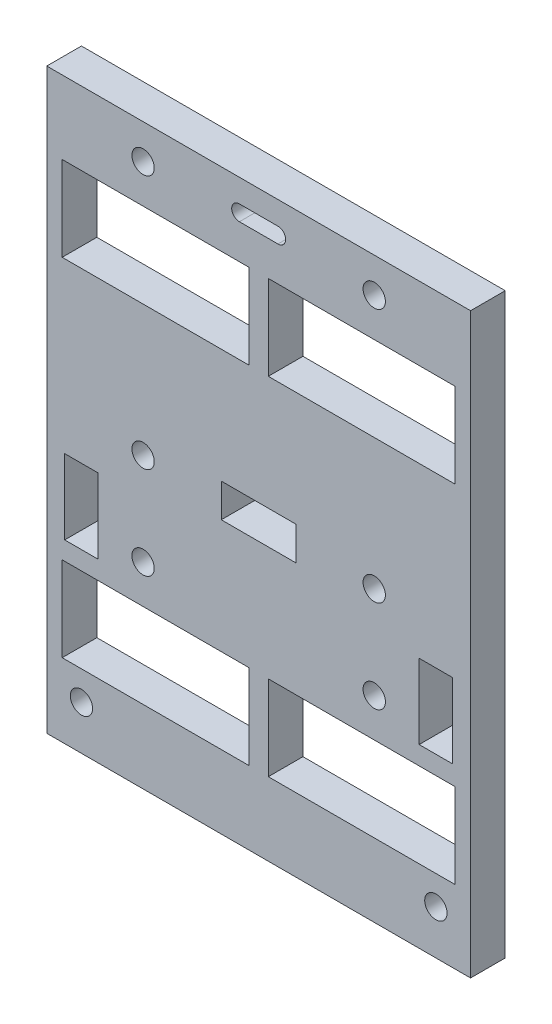
SolidWorks part; units mm, degrees
ref_plane "Front Plane" through (0, 0, 0) normal (0, 0, 1) x (1, 0, 0)
ref_plane "Top Plane" through (0, 0, 0) normal (0, 1, 0) x (1, 0, 0)
ref_plane "Right Plane" through (0, 0, 0) normal (1, 0, 0) x (0, 0, -1)
sketch "Sketch1" plane through (0, 0, 0) normal (0, 0, 1) x (1, 0, 0)
  line L0 (0, -37.5) -> (0, 37.5) construction
  line L1 (-27.5, -37.5) -> (27.5, -37.5)
  line L2 (-27.5, -37.5) -> (-27.5, 37.5)
  line L3 (-27.5, 37.5) -> (27.5, 37.5)
  line L4 (27.5, -37.5) -> (27.5, 37.5)
  line L5 (-27.5, -37.5) -> (27.5, 37.5) construction
  line L6 (-27.5, 37.5) -> (27.5, -37.5) construction
  line L7 (-27.5, 0) -> (27.5, 0) construction
  line L8 (-27.5, 22.5) -> (27.5, 22.5) construction
  line L9 (25.5, 17) -> (1.25, 28) construction
  line L10 (-25.5, 28) -> (-1.25, 28)
  line L11 (-25.5, 28) -> (-25.5, 17)
  line L12 (-25.5, 17) -> (-1.25, 17)
  line L13 (-1.25, 28) -> (-1.25, 17)
  line L14 (-25.5, 28) -> (-1.25, 17) construction
  line L15 (-25.5, 17) -> (-1.25, 28) construction
  line L16 (25.5, 28) -> (1.25, 17) construction
  line L17 (1.25, 28) -> (1.25, 17)
  line L18 (25.5, 17) -> (1.25, 17)
  line L19 (25.5, 28) -> (25.5, 17)
  line L20 (25.5, 28) -> (1.25, 28)
  line L21 (25.5, -28) -> (1.25, -17) construction
  line L22 (-25.5, -17) -> (-1.25, -28) construction
  line L23 (-25.5, -28) -> (-1.25, -17) construction
  line L24 (25.5, -17) -> (1.25, -28) construction
  line L25 (25.5, -28) -> (1.25, -28)
  line L26 (25.5, -28) -> (25.5, -17)
  line L27 (25.5, -17) -> (1.25, -17)
  line L28 (1.25, -28) -> (1.25, -17)
  line L29 (-1.25, -28) -> (-1.25, -17)
  line L30 (-25.5, -17) -> (-1.25, -17)
  line L31 (-25.5, -28) -> (-25.5, -17)
  line L32 (-25.5, -28) -> (-1.25, -28)
  point P0 (0, 0)
  point P12 (-13.375, 22.5)
  point P21 (13.375, 22.5)
  point P30 (13.375, -22.5)
  point P31 (-13.375, -22.5)
  dimension "D1" = 55
  dimension "D2" = 75
  dimension "D3" = 22.5
  dimension "D4" = 24.25
  dimension "D5" = 11
  dimension "D6" = 1.25
extrude "Boss-Extrude1" add sketch "Sketch1" along normal blind 4.5
sketch "Sketch2" plane through (0, 0, 4.5) normal (0, 0, 1) x (1, 0, 0)
  line L0 (0, -37.5) -> (0, 37.5) construction
  line L1 (-27.5, -37.5) -> (27.5, -37.5) construction
  line L2 (27.5, 37.5) -> (-27.5, 37.5) construction
  line L3 (-27.5, 0) -> (27.5, 0) construction
  line L4 (-27.5, 37.5) -> (-27.5, -37.5) construction
  line L5 (27.5, -37.5) -> (27.5, 37.5) construction
  line L6 (-15, 0) -> (15, 0) construction
  circle A0 centre (-15, 33) radius 1.45
  circle A1 centre (15, 33) radius 1.45
  circle A2 centre (15, 0) radius 1.45
  circle A3 centre (-15, 0) radius 1.45
  dimension "D1" = 2.9
  dimension "D7" = 2.9
  dimension "D8" = 2.9
  dimension "D2" = 15
  dimension "D3" = 33
  dimension "D4" = 30
  dimension "D5" = 15
  dimension "D6" = 0
extrude "screwHoles" cut sketch "Sketch2" against normal through all
sketch "Sketch3" plane through (0, 0, 4.5) normal (0, 0, 1) x (1, 0, 0)
  line L0 (-27.5, 9) -> (26.0486, 9) construction
  line L1 (-27.5, 37.5) -> (-27.5, -37.5) construction
  line L3 (0, 37.5) -> (0, -37.5) construction
  line L4 (27.5, 37.5) -> (-27.5, 37.5) construction
  line L5 (-27.5, -37.5) -> (27.5, -37.5) construction
  line L6 (18.95, 6.8) -> (9.05, 11.2) construction
  line L7 (-18.95, 11.2) -> (-9.05, 11.2)
  line L8 (-18.95, 11.2) -> (-18.95, 6.8)
  line L9 (-18.95, 6.8) -> (-9.05, 6.8)
  line L10 (-9.05, 11.2) -> (-9.05, 6.8)
  line L11 (-18.95, 11.2) -> (-9.05, 6.8) construction
  line L12 (-18.95, 6.8) -> (-9.05, 11.2) construction
  line L13 (18.95, 11.2) -> (9.05, 6.8) construction
  line L14 (9.05, 11.2) -> (9.05, 6.8)
  line L15 (18.95, 6.8) -> (9.05, 6.8)
  line L16 (18.95, 11.2) -> (18.95, 6.8)
  line L17 (18.95, 11.2) -> (9.05, 11.2)
  line L18 (-27.5, 37.5) -> (-27.5, -37.5) construction
  point P2 (-27.5, 0)
  point P12 (-14, 9)
  point P21 (14, 9)
  dimension "D1" = 9.9
  dimension "D3" = 14
  dimension "D4" = 9
extrude "BeltClamp" [suppressed] cut sketch "Sketch3" against normal through all
sketch "Sketch4" plane through (0, 0, 4.5) normal (0, 0, 1) x (1, 0, 0)
  line L0 (-27.5, 0) -> (27.5, 0) construction
  line L1 (-27.5, 37.5) -> (-27.5, -37.5) construction
  line L2 (27.5, -37.5) -> (27.5, 37.5) construction
  line L4 (-4.85, 2.175) -> (4.85, 2.175)
  line L5 (-4.85, 2.175) -> (-4.85, -2.175)
  line L6 (-4.85, -2.175) -> (4.85, -2.175)
  line L7 (4.85, 2.175) -> (4.85, -2.175)
  line L8 (-4.85, 2.175) -> (4.85, -2.175) construction
  line L9 (-4.85, -2.175) -> (4.85, 2.175) construction
  circle A0 centre (-15, 0) radius 1.45 construction
  point P6 (0, 0)
  dimension "D2" = 4.35
  dimension "D3" = 0
extrude "mountingPlateTab" cut sketch "Sketch4" against normal through all
sketch "Sketch5" plane through (0, 0, 4.5) normal (0, 0, 1) x (1, 0, 0)
  line L0 (-27.5, -9.75) -> (27.5, -9.75) construction
  line L1 (-27.5, 37.5) -> (-27.5, -37.5) construction
  line L2 (27.5, -37.5) -> (27.5, 37.5) construction
  line L4 (0, -37.5) -> (0, 37.5) construction
  line L5 (-27.5, -37.5) -> (27.5, -37.5) construction
  line L6 (27.5, 37.5) -> (-27.5, 37.5) construction
  line L7 (-20.825, -14.6) -> (-25.175, -4.9) construction
  line L8 (20.825, -4.9) -> (25.175, -4.9)
  line L9 (20.825, -4.9) -> (20.825, -14.6)
  line L10 (20.825, -14.6) -> (25.175, -14.6)
  line L11 (25.175, -4.9) -> (25.175, -14.6)
  line L12 (20.825, -4.9) -> (25.175, -14.6) construction
  line L13 (20.825, -14.6) -> (25.175, -4.9) construction
  line L14 (-20.825, -4.9) -> (-25.175, -14.6) construction
  line L15 (-25.175, -4.9) -> (-25.175, -14.6)
  line L16 (-20.825, -14.6) -> (-25.175, -14.6)
  line L17 (-20.825, -4.9) -> (-20.825, -14.6)
  line L18 (-20.825, -4.9) -> (-25.175, -4.9)
  line L19 (23, -9.75) -> (23, -37.5) construction
  line L20 (-23, -9.75) -> (-23, -37.5) construction
  circle A0 centre (23, -31.75) radius 1.45
  circle A1 centre (-23, -31.75) radius 1.45
  point P15 (23, -9.75)
  point P24 (-23, -9.75)
  dimension "D5" = 2.9
  dimension "D2" = 9.7
  dimension "D3" = 4.35
  dimension "D4" = 23
  dimension "D6" = 22
  dimension "D1" = 9.75
extrude "BraceTabs" cut sketch "Sketch5" against normal through all
sketch "Sketch6" plane through (0, 0, 4.5) normal (0, 0, 1) x (1, 0, 0)
  line L0 (-25.175, -9.75) -> (25.175, -9.75) construction
  line L1 (-25.175, -4.9) -> (-25.175, -14.6) construction
  line L2 (25.175, -14.6) -> (25.175, -4.9) construction
  line L3 (0, -2.175) -> (0, -37.5) construction
  line L4 (-4.85, -2.175) -> (4.85, -2.175) construction
  line L5 (-27.5, -37.5) -> (27.5, -37.5) construction
  line L6 (23, -14.6) -> (23, -4.9) construction
  line L7 (20.825, -14.6) -> (25.175, -14.6) construction
  line L8 (25.175, -4.9) -> (20.825, -4.9) construction
  line L9 (20.825, -4.9) -> (20.825, -14.6) construction
  line L10 (19.825, -15.6) -> (26.175, -15.6)
  line L11 (19.825, -15.6) -> (19.825, -3.9)
  line L12 (19.825, -3.9) -> (26.175, -3.9)
  line L13 (26.175, -15.6) -> (26.175, -3.9)
  line L14 (19.825, -15.6) -> (26.175, -3.9) construction
  line L15 (19.825, -3.9) -> (26.175, -15.6) construction
  line L16 (-19.825, -3.9) -> (-26.175, -15.6) construction
  line L17 (-19.825, -15.6) -> (-26.175, -3.9) construction
  line L18 (-23, -14.6) -> (-23, -4.9) construction
  line L19 (-26.175, -15.6) -> (-26.175, -3.9)
  line L20 (-19.825, -3.9) -> (-26.175, -3.9)
  line L21 (-19.825, -15.6) -> (-19.825, -3.9)
  line L22 (-19.825, -15.6) -> (-26.175, -15.6)
  circle A0 centre (23, -9.75) radius 1.45
  circle A1 centre (-23, -9.75) radius 1.45
  point P18 (23, -9.75)
  dimension "D3" = 2.9
  dimension "D1" = 1
  dimension "D2" = 1
extrude "FrontToRear1" [suppressed] add sketch "Sketch6" against normal up to surface (4.5 mm away) up to face at (-24.45, -31.75, 0)
sketch "Sketch7" plane through (0, 0, 4.5) normal (0, 0, 1) x (1, 0, 0)
  line L0 (4.85, 2.175) -> (-4.85, 2.175) construction
  line L1 (-20, -3.175) -> (20, -3.175)
  line L2 (-20, -3.175) -> (-20, 3.175)
  line L3 (-20, 3.175) -> (20, 3.175)
  line L4 (20, -3.175) -> (20, 3.175)
  line L5 (-20, -3.175) -> (20, 3.175) construction
  line L6 (-20, 3.175) -> (20, -3.175) construction
  circle A0 centre (15, 0) radius 1.45 construction
  point P0 (0, 0)
  dimension "D1" = 1
  dimension "D2" = 5
extrude "FrontToRear2" [suppressed] add sketch "Sketch7" against normal through all
sketch "Sketch8" plane through (0, 0, 4.5) normal (0, 0, 1) x (1, 0, 0)
  line L0 (-27.5, -12) -> (27.5, -12) construction
  line L1 (-27.5, 37.5) -> (-27.5, -37.5) construction
  line L2 (27.5, -37.5) -> (27.5, 37.5) construction
  line L3 (0, -37.5) -> (0, 0) construction
  line L4 (-27.5, -37.5) -> (27.5, -37.5) construction
  circle A0 centre (-15, -12) radius 1.45
  circle A1 centre (15, -12) radius 1.45
  dimension "D2" = 2.9
  dimension "D1" = 12
  dimension "D3" = 15
extrude "ExpansionScrewholes" cut sketch "Sketch8" against normal through all
sketch "Sketch12" plane through (0, 0, 4.5) normal (0, 0, 1) x (1, 0, 0)
  line L0 (0, 37.5) -> (0, 0) construction
  line L1 (27.5, 37.5) -> (-27.5, 37.5) construction
  line L2 (-2.5, 33.5) -> (2.5, 33.5) construction
  line L3 (-2.5, 34.5) -> (2.5, 34.5)
  line L4 (-2.5, 32.5) -> (2.5, 32.5)
  arc A0 (-2.5, 34.5) -> (-2.5, 32.5) centre (-2.5, 33.5) ccw
  arc A1 (2.5, 32.5) -> (2.5, 34.5) centre (2.5, 33.5) ccw
  point P7 (0, 33.5)
  dimension "D1" = 3
  dimension "D2" = 2
  dimension "D3" = 5
extrude "CableTieSlot" cut sketch "Sketch12" against normal through all
sketch "Sketch11" [suppressed] plane through (0, 0, 4.5) normal (0, 0, 1) x (1, 0, 0)
  line L0 (13.5615, -8.85) -> (27.5, -8.85) construction
  line L1 (27.5, -37.5) -> (27.5, 37.5) construction
  line L2 (0, 37.5) -> (0, -37.5) construction
  line L3 (36.5, -14.85) -> (18.5, -14.85)
  line L4 (36.5, -14.85) -> (36.5, -2.85)
  line L5 (36.5, -2.85) -> (18.5, -2.85)
  line L6 (18.5, -14.85) -> (18.5, -2.85)
  line L7 (36.5, -14.85) -> (18.5, -2.85) construction
  line L8 (36.5, -2.85) -> (18.5, -14.85) construction
  line L11 (-36.5, -2.85) -> (-18.5, -14.85) construction
  line L12 (-36.5, -14.85) -> (-18.5, -2.85) construction
  line L13 (-18.5, -14.85) -> (-18.5, -2.85)
  line L14 (-36.5, -2.85) -> (-18.5, -2.85)
  line L15 (-36.5, -14.85) -> (-36.5, -2.85)
  line L16 (-36.5, -14.85) -> (-18.5, -14.85)
  line L17 (36.5, -2.85) -> (18.5, -14.85) construction
  line L18 (20.65, -14.85) -> (25.35, -14.85) construction
  line L19 (27.5, 37.5) -> (-27.5, 37.5) construction
  line L20 (-27.5, -37.5) -> (27.5, -37.5) construction
  dimension "D1" = 9
  dimension "D2" = 12
  dimension "D3" = 0
extrude "Cut-Extrude2" [suppressed] cut sketch "Sketch11" against normal through all
sketch "Sketch10" plane through (0, 0, 4.5) normal (0, 0, 1) x (1, 0, 0)
  line L0 (4.7446, 1) -> (27.5, 1) construction
  line L1 (-4.85, 0) -> (4.85, 0) construction
  line L2 (27.5, -37.5) -> (27.5, 37.5) construction
  line L3 (0, 2.175) -> (0, -2.175) construction
  line L4 (36.5, 4) -> (18.5, 4)
  line L5 (36.5, 4) -> (36.5, -2)
  line L6 (36.5, -2) -> (18.5, -2)
  line L7 (18.5, 4) -> (18.5, -2)
  line L8 (36.5, 4) -> (18.5, -2) construction
  line L9 (36.5, -2) -> (18.5, 4) construction
  line L10 (4.85, 2.175) -> (-4.85, 2.175) construction
  line L11 (-4.85, -2.175) -> (4.85, -2.175) construction
  line L12 (-36.5, -2) -> (-18.5, 4) construction
  line L13 (-36.5, 4) -> (-18.5, -2) construction
  line L14 (-4.7446, 1) -> (-27.5, 1) construction
  line L15 (-18.5, 4) -> (-18.5, -2)
  line L16 (-36.5, -2) -> (-18.5, -2)
  line L17 (-36.5, 4) -> (-36.5, -2)
  line L18 (-36.5, 4) -> (-18.5, 4)
  line L19 (36.5, -2) -> (18.5, 4) construction
  line L20 (-4.85, 2.175) -> (-4.85, -2.175) construction
  line L21 (4.85, -2.175) -> (4.85, 2.175) construction
  dimension "D1" = 6
  dimension "D2" = 9
  dimension "D3" = 1
extrude "CableTieSlots" [suppressed] cut sketch "Sketch10" against normal through all
sketch "Sketch9" [suppressed] plane through (0, 0, 4.5) normal (0, 0, 1) x (1, 0, 0)
  line L0 (-27.5, -37.5) -> (27.5, -37.5) construction
  line L5 (-9, -42.5) -> (9, -42.5)
  line L6 (-9, -42.5) -> (-9, -34.5)
  line L7 (-7, -32.5) -> (7, -32.5)
  line L8 (9, -42.5) -> (9, -34.5)
  line L9 (-9, -42.5) -> (9, -32.5) construction
  line L10 (-9, -32.5) -> (9, -42.5) construction
  arc A0 (7, -32.5) -> (9, -34.5) centre (7, -34.5) cw
  arc A1 (-9, -34.5) -> (-7, -32.5) centre (-7, -34.5) cw
  point P9 (0, -37.5)
  dimension "D3" = 2
  dimension "D1" = 18
  dimension "D2" = 5
extrude "RearFanSlot" [suppressed] cut sketch "Sketch9" against normal through all
sketch "Sketch13" [suppressed] plane through (0, 0, 4.5) normal (0, 0, 1) x (1, 0, 0)
  line L1 (-7, -2.85) -> (7, -2.85)
  line L2 (-7, -2.85) -> (-7, -11.85)
  line L3 (-7, -11.85) -> (7, -11.85)
  line L4 (7, -2.85) -> (7, -11.85)
  line L5 (-7, -2.85) -> (7, -11.85) construction
  line L6 (-7, -11.85) -> (7, -2.85) construction
  line L9 (0, 37.5) -> (0, -7.35) construction
  line L10 (-18.5, -2.85) -> (-27.5, -2.85) construction
  line L11 (27.5, 37.5) -> (-27.5, 37.5) construction
  line L13 (-27.5, -14.85) -> (-18.5, -14.85) construction
  point P0 (0, -7.35)
  dimension "D1" = 3
  dimension "D2" = 0
  dimension "D3" = 7
extrude "Cut-Extrude3" [suppressed] cut sketch "Sketch13" against normal through all
sketch "Sketch14" [suppressed] plane through (0, 0, 4.5) normal (0, 0, 1) x (1, 0, 0)
  line L0 (25.2, -4.85) -> (20.8, -4.85) construction
  line L1 (25.2, -4.85) -> (20.8, -4.85)
  line L2 (25.2, -4.85) -> (25.2, -14.65)
  line L3 (25.2, -14.65) -> (20.8, -14.65)
  line L4 (20.8, -4.85) -> (20.8, -14.65)
  line L5 (25.2, -14.65) -> (25.2, -4.85) construction
  line L6 (0, 0) -> (0, -6.835) construction
  line L7 (-20.8, -4.85) -> (-20.8, -14.65)
  line L8 (-25.2, -14.65) -> (-20.8, -14.65)
  line L9 (-25.2, -4.85) -> (-25.2, -14.65)
  line L10 (-25.2, -4.85) -> (-20.8, -4.85)
extrude "Boss-Extrude2" [suppressed] add sketch "Sketch14" against normal through all
equation "\"X-ROD-SPACING\"=45"
equation "\"Y-ROD-SPACING\"=75"
equation "\"Z-ROD-SPACING\"=17.5"
equation "\"Y-BED-OFFSET\"=2"
equation "\"Y-BED-ROD-INSET\"=3.5"
equation "\"Y-BED-SCREW-SPACING\"=209"
equation "\"Y-BED-SCREW-CUTOUT-SLOT-HEIGHT\"=2.5"
equation "\"T-SLOT-NUT-FILLET-RADIUS\"=0.5"
equation "\"T-SLOT-SCREW-SHAFT-RADIUS\"=1.55"
equation "\"T-SLOT-SCREW-SHAFT-CUTOUT-LENGTH\"=11"
equation "\"T-SLOT-NUT-DEPTH\"=3.5"
equation "\"T-SLOT-NUT-WIDTH\"=2.85"
equation "\"T-SLOT-NUT-END-DISTANCE\"=8"
equation "\"ACRYLIC-THICKNESS\"=10"
equation "\"ACRYLIC-THICKNESS2\"=4.5"
equation "\"ACRYLIC-TAB-CUTOUT-SIZE\"=\"ACRYLIC-THICKNESS\"+\"ACRYLIC-TAB-TOLERANCE\"*2"
equation "\"ACRYLIC-TAB-WIDTH\"=\"ACRYLIC-THICKNESS\""
equation "\"ACRYLIC-M3-HOLE\"=2.9"
equation "\"SMOOTHROD-CAP-SCREW-DISTANCE\"=20"
equation "\"FRAME-WIDTH-INNER\"=370"
equation "\"NEMA17-HOLE-SPACING\"=31"
equation "\"NEMA17-CENTRAL-CUTOUT\"=22.5"
equation "\"Z-BRACKET-REACH\"=57"
equation "\"Z-ROD-INSET\"=13.5"
equation "\"TOP-BRACKET-SPACING\"=40"
equation "\"SMOOTHROD-X-LENGTH\"=350"
equation "\"SMOOTHROD-Y-LENGTH\"=350"
equation "\"SMOOTHROD-Z-LENGTH\"=350"
equation "\"SMOOTHROD-TIGHTENING-HEADROOM\"=.25"
equation "\"LEADSCREW-Z-LENGTH\"=300"
equation "\"SCREW-LENGTH-FRAME\"=\"ACRYLIC-THICKNESS\" + 10"
equation "\"SCREW-LENGTH-MOTOR\"=\"ACRYLIC-THICKNESS\" + 5"
equation "\"SCREW-HEAD-RADIUS\"=6"
equation "\"PRINTED-X-SMOOTHROD-DIAMETER\"=8.8"
equation "\"PRINTED-X-SMOOTHROD-CUTOUT\"=10"
equation "\"PRINTED-X-BASE-HEIGHT\"=10"
equation "\"PRINTED-LM8UU-CUTOUT-SIZE\"=15.5"
equation "\"PRINTED-LM8UU-CUTOUT-LENGTH\"=24.5"
equation "\"PRINTED-X-IDLER-HEIGHT\"=16"
equation "\"PSU-MOUNTING-WIDTH\"=95"
equation "\"PSU-MOUNTING-HEIGHT\"=177"
equation "\"Y-BELT-TO-ROD-DISTANCE\"=20"
equation "\"SPOOL-HOLDER-ROD-SPACING\"=150"
equation "\"D3@Sketch1\"=\"X-ROD-SPACING\"/2"
equation "\"D4@Sketch1\"=\"ACRYLIC-X-CARRIAGE-LM8UU-CUTOUT-WIDTH\""
equation "\"D1@Boss-Extrude1\"=\"ACRYLIC-THICKNESS2\""
equation "\"D1@Sketch2\"=\"ACRYLIC-M3-HOLE\""
equation "\"D1@Sketch3\"=\"ACRYLIC-TAB-CUTOUT-SIZE\""
equation "\"D2@Sketch3\"=\"ACRYLIC-THICKNESS2\"+\"ACRYLIC-TAB-TOLERANCE\"*2"
equation "\"ACRYLIC-X-CARRIAGE-WIDTH\"=55"
equation "\"ACRYLIC-X-CARRIAGE-HEIGHT\"=75"
equation "\"D1@Sketch1\"=\"ACRYLIC-X-CARRIAGE-WIDTH\""
equation "\"D2@Sketch1\"=\"ACRYLIC-X-CARRIAGE-HEIGHT\""
equation "\"ACRYLIC-X-CARRIAGE-CENTER-TAB-SPACING\"=14"
equation "\"D3@Sketch3\"=\"ACRYLIC-X-CARRIAGE-CENTER-TAB-SPACING\""
equation "\"SCREW-LENGTH-EXTRUDER\"=28"
equation "\"ACRYLIC-X-CARRIAGE-SCREW-SPACING-X\"=15"
equation "\"ACRYLIC-X-CARRIAGE-SCREW-SPACING-Y\"=33"
equation "\"D2@Sketch2\"=\"ACRYLIC-X-CARRIAGE-SCREW-SPACING-X\""
equation "\"D3@Sketch2\"=\"ACRYLIC-X-CARRIAGE-SCREW-SPACING-Y\""
equation "\"D1@Sketch4\"=\"ACRYLIC-TAB-WIDTH\"-\"KERF\"*4"
equation "\"D2@Sketch4\"=\"ACRYLIC-THICKNESS2\"-\"KERF\"*2"
equation "\"D2@Sketch5\"=\"ACRYLIC-TAB-WIDTH\"-\"KERF\"*4"
equation "\"D3@Sketch5\"=\"ACRYLIC-THICKNESS2\"-\"KERF\"*2"
equation "\"ACRYLIC-X-CARRIAGE-EXTRUDER-SHELF-DEPTH\"=\"ACRYLIC-X-CARRIAGE-EXTRUDER-OFFSET\" + 28"
equation "\"ACRYLIC-X-CARRIAGE-EXTRUDER-BRACE-SPACING\"=23"
equation "\"D4@Sketch5\"=\"ACRYLIC-X-CARRIAGE-EXTRUDER-BRACE-SPACING\""
equation "\"D4@Sketch2\"=\"ACRYLIC-X-CARRIAGE-SCREW-SPACING-X\"*2"
equation "\"D5@Sketch2\"=\"ACRYLIC-X-CARRIAGE-SCREW-SPACING-X\""
equation "\"D7@Sketch2\"=\"ACRYLIC-M3-HOLE\""
equation "\"D8@Sketch2\"=\"ACRYLIC-M3-HOLE\""
equation "\"ACRYLIC-X-CARRIAGE-LM8UU-CUTOUT-WIDTH\"=24.25"
equation "\"ACRYLIC-TAB-TOLERANCE\"=-.05"
equation "\"ACRYLIC-X-CARRIAGE-EXTRUDER-OFFSET\"=26"
equation "\"ACRYLIC-X-CARRIAGE-EXTRUDER-ANGLE\"=90"
equation "\"ACRYLIC-X-CARRIAGE-EXTRUDER-BRACE-TAB-OFFSET\"=20"
equation "\"ACRYLIC-X-CARRIAGE-EXTRUDER-BRACE-HEIGHT\"=35"
equation "\"ACRYLIC-X-CARRIAGE-EXTRUDER-BRACE-SCREW-SPACING\"=22"
equation "\"D5@Sketch5\"=\"ACRYLIC-M3-HOLE\""
equation "\"D3@Sketch6\"=\"ACRYLIC-M3-HOLE\""
equation "\"ACRYLIC-X-CARRIAGE-LM8UU-CUTOUT-HEIGHT\"=11.0"
equation "\"ACRYLIC-X-CARRIAGE-DUAL-WIDTH-MULTIPLIER\"=1.65"
equation "\"ACRYLIC-X-CARRIAGE-DUAL-HOTEND-SPACING\"=42"
equation "\"ACRYLIC-X-CARRIAGE-DUAL-WIDTH\"=75"
equation "\"ACRYLIC-X-CARRIAGE-DUAL-HOTEND-SEPARATION\"=36"
equation "\"ACRYLIC-X-CARRIAGE-DUAL-MOUNT-PLATE-DEPTH\"=75"
equation "\"ACRYLIC-X-CARRIAGE-DUAL-MOUNT-BRACE-WIDTH\"=33"
equation "\"ACRYLIC-X-CARRIAGE-DUAL-MOUNT-SCREW-WIDTH\"=40"
equation "\"D5@Sketch1\"=\"ACRYLIC-X-CARRIAGE-LM8UU-CUTOUT-HEIGHT\""
equation "\"D2@Sketch8\"=\"ACRYLIC-M3-HOLE\""
equation "\"D1@Sketch5\"=\"ACRYLIC-THICKNESS2\"/2 + 7.5"
equation "\"KERF\"=0.075"
equation "\"PRINTED-M3-HOLE\"=3.5"
equation "\"PRINTED-M3-NUT-AF\"=6.25"
equation "\"ACRYLIC-X-CARRIAGE-DUAL-FAN-OFFSET\"=52"
equation "\"ACRYLIC-X-CARRIAGE-DUAL-FAN-HEIGHT\"=20"
equation "\"BLOWER-FAN-WIDTH\"=15"
